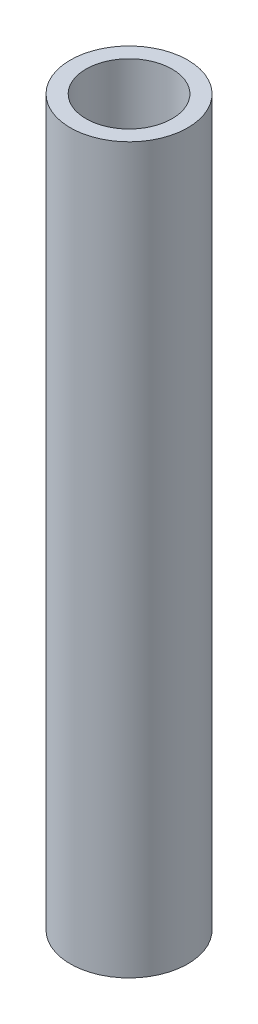
SolidWorks part; units mm, degrees
ref_plane "Front Plane" through (0, 0, 0) normal (0, 0, 1) x (1, 0, 0)
ref_plane "Top Plane" through (0, 0, 0) normal (0, 1, 0) x (1, 0, 0)
ref_plane "Right Plane" through (0, 0, 0) normal (1, 0, 0) x (0, 0, -1)
sketch "Sketch2" plane through (0, 0, 0) normal (0, 0, 1) x (1, 0, 0)
  line L0 (0, 0) -> (0, 117.475) construction
  line L1 (-3.9688, 0) -> (0, 0) construction
  line L2 (-3.9688, 0) -> (-3.9688, 12.7)
  line L3 (-3.9688, 12.7) -> (-6.985, 12.7)
  line L4 (-6.985, 12.7) -> (-6.985, 117.475)
  line L5 (-6.985, 117.475) -> (-9.525, 117.475)
  line L6 (-9.525, 117.475) -> (-9.525, 0)
  line L7 (-9.525, 0) -> (-3.9688, 0)
  line L8 (-6.985, 117.475) -> (0, 117.475) construction
  dimension "D1" = 3.9688
  dimension "D2" = 9.525
  dimension "D3" = 2.54
  dimension "D4" = 117.475
  dimension "D5" = 12.7
revolve "Revolve1" add sketch "Sketch2" angle 360 about L0
thread "Thread1" pitch 1.0583 method cut profile "Thread Profile1" start angle 0, offset 0, length 25.4, pitch 1.0583, diameter 7.9375
ref_plane "Plane1" through (3.9688, 0, 0) normal (0, 0, 1) x (1, 0, 0)
sketch "Thread Profile1" plane through (3.9688, 0, 0) normal (0, 0, 1) x (1, 0, 0)
  line L0 (0, 0) -> (0, 1.0583) construction
  line L1 (0, 0) -> (0.5728, 0.3307)
  line L2 (0.5728, 0.3307) -> (0.5728, 0.463)
  line L3 (0.5728, 0.463) -> (0, 0.7937)
  line L4 (0.5728, 0.3969) -> (0, 0.3969) construction
  line L11 (0, 0) -> (0, 0.7937)
  point P2 (0, 0)
  dimension "Pitch" = 1.0583
  dimension "Profile_Angle" = 60
  dimension "Profile_Land" = 0.1323
  dimension "Profile_Height" = 0.5728
sketch3d "3DSketch1"
  line L0 (0, 117.475, 0) -> (0, 0, 0) construction
  line L1 (0, 117.475, 0) -> (0, 12.7, 0) construction
  line L2 (0, 117.475, 0) -> (0, 0, 0) construction
